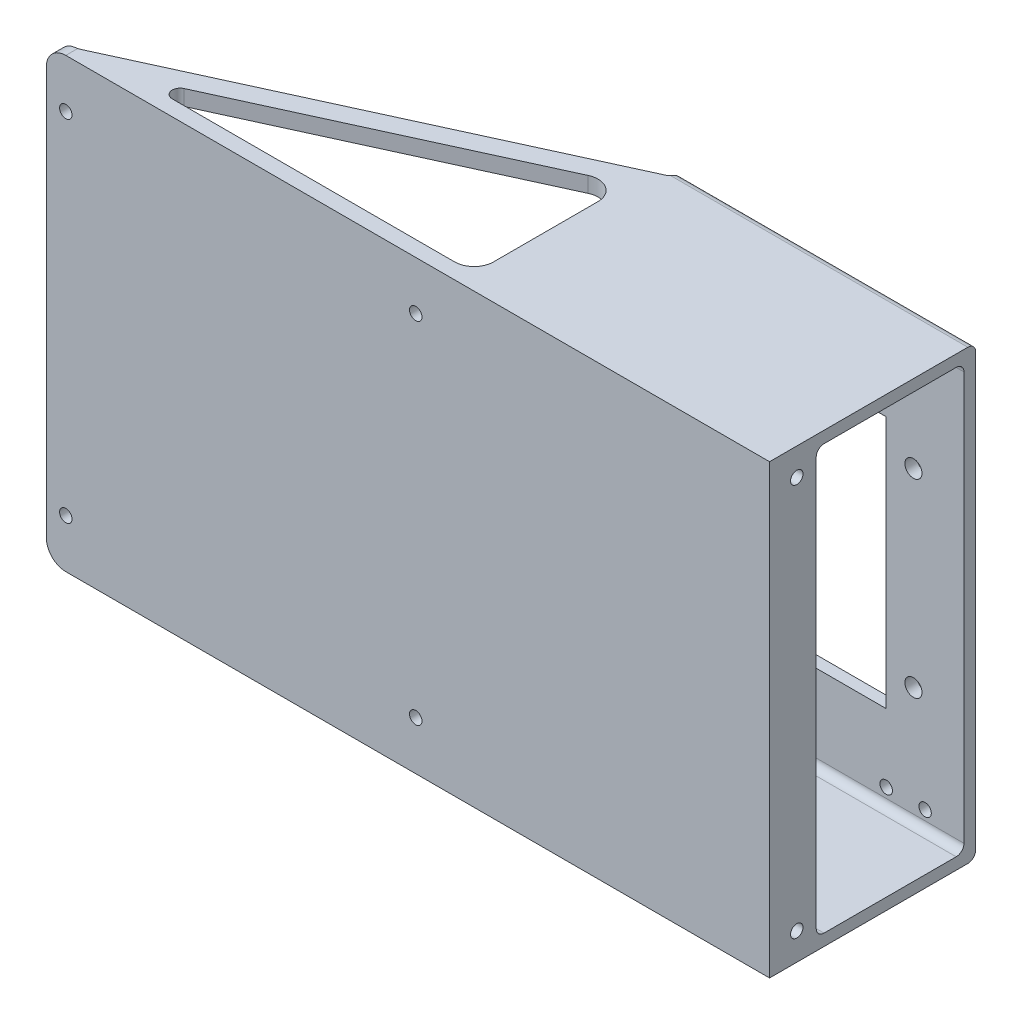
SolidWorks part; units mm, degrees
ref_plane "前视基准面" through (0, 0, 0) normal (0, 0, 1) x (1, 0, 0)
ref_plane "上视基准面" through (0, 0, 0) normal (0, 1, 0) x (1, 0, 0)
ref_plane "右视基准面" through (0, 0, 0) normal (1, 0, 0) x (0, 0, -1)
sketch "草图2" plane through (0, 0, 0) normal (0, 0, 1) x (1, 0, 0)
  line L4 (37.2625, -42.4817) -> (86.0528, -91.2721) construction
  line L5 (23.0528, -9.4817) -> (99.0528, -9.4817)
  line L6 (23.0528, -9.4817) -> (23.0528, -124.4817)
  line L7 (23.0528, -124.4817) -> (99.0528, -124.4817)
  line L8 (99.0528, -9.4817) -> (99.0528, -124.4817)
  line L9 (86.0528, -42.4817) -> (37.2625, -91.2721) construction
  circle A0 centre (86.0528, -91.2721) radius 2.2
  circle A1 centre (86.0528, -42.4817) radius 2.2
  circle A2 centre (37.2625, -42.4817) radius 2.2
  circle A3 centre (37.2625, -91.2721) radius 2.2
  circle A4 centre (89.0528, -16.9817) radius 1.6
  circle A5 centre (79.0528, -16.9817) radius 1.6
  circle A6 centre (41.0528, -16.9817) radius 1.6
  circle A7 centre (51.0528, -16.9817) radius 1.6
  circle A8 centre (41.0528, -116.9817) radius 1.6
  circle A9 centre (51.0528, -116.9817) radius 1.6
  circle A10 centre (79.0528, -116.9817) radius 1.6
  circle A11 centre (89.0528, -116.9817) radius 1.6
  point P12 (64.3101, -80.4099)
  dimension "D4" = 90
  dimension "D5" = 13
  dimension "D6" = 33
  dimension "D7" = 69
  dimension "D8" = 3.2
  dimension "D3" = 69
  dimension "D9" = 10
  dimension "D10" = 7.5
  dimension "D11" = 4.4
  dimension "D12" = 4.4
  dimension "D13" = 4.4
  dimension "D14" = 4.4
  dimension "D18" = 100
  dimension "D1" = 115
  dimension "D2" = 76
  dimension "D15" = 2
  dimension "D16" = 2
  dimension "D17" = 2
extrude "凸台-拉伸1" add sketch "草图2" along normal blind 3
sketch "草图3" plane through (23.0528, 0, 0) normal (-1, 0, 0) x (0, 0, 1)
  line L0 (0, -9.4817) -> (0, -124.4817) construction
  line L1 (0, -9.4817) -> (53, -9.4817)
  line L2 (0, -9.4817) -> (0, -12.4817)
  line L3 (0, -12.4817) -> (50, -12.4817)
  line L8 (50, -12.4817) -> (50, -121.4817)
  line L9 (53, -124.4817) -> (0, -124.4817)
  line L11 (50, -121.4817) -> (0, -121.4817)
  line L12 (0, -124.4817) -> (0, -121.4817)
  line L13 (53, -124.4817) -> (53, -9.4817)
  dimension "D1" = 115
  dimension "D2" = 3
  dimension "D4" = 50
extrude "凸台-拉伸2" add sketch "草图3" against normal blind 76
sketch "草图4" plane through (23.0528, 0, 0) normal (-1, 0, 0) x (0, 0, 1)
  line L0 (3, -12.4817) -> (50, -12.4817) construction
  line L1 (3, -12.4817) -> (50, -12.4817)
  line L2 (3, -12.4817) -> (3, -121.4817)
  line L3 (3, -121.4817) -> (50, -121.4817)
  line L4 (50, -12.4817) -> (50, -121.4817)
  line L5 (3, -12.4817) -> (3, -121.4817) construction
extrude "凸台-拉伸3" add sketch "草图4" against normal blind 3
sketch "草图5" plane through (99.0528, 0, 0) normal (1, 0, 0) x (0, 0, -1)
  line L0 (-53, -124.4817) -> (0, -124.4817) construction
  line L1 (-53, -9.4817) -> (-41, -9.4817)
  line L2 (-53, -9.4817) -> (-53, -124.4817)
  line L3 (-53, -124.4817) -> (-41, -124.4817)
  line L4 (-41, -9.4817) -> (-41, -124.4817)
  circle A0 centre (-46, -117.4817) radius 1.6
  circle A1 centre (-46, -16.4817) radius 1.6
  dimension "D2" = 5
  dimension "D3" = 7
  dimension "D4" = 5
  dimension "D5" = 7
  dimension "D1" = 12
extrude "凸台-拉伸4" add sketch "草图5" against normal blind 3
fillet "圆角1" radius 2 8 edges at (97.5528, -121.4817, 41) (97.5528, -12.4817, 41) (61.0528, -12.4817, 50) (61.0528, -121.4817, 50) (62.5528, -121.4817, 3) (61.0528, -124.4817, 0) (61.0528, -9.4817, 0) (62.5528, -12.4817, 3)
sketch "草图6" plane through (23.0528, 0, 0) normal (-1, 0, 0) x (0, 0, 1)
  line L1 (53, -9.4817) -> (50, -9.4817)
  line L2 (53, -9.4817) -> (53, -124.4817)
  line L3 (53, -124.4817) -> (50, -124.4817)
  line L4 (50, -9.4817) -> (50, -124.4817)
  point P7 (0, 0)
  point P8 (0, 0)
  dimension "D1" = 3
  dimension "D2" = 115
extrude "凸台-拉伸5" add sketch "草图6" along normal blind 110
sketch "草图7" plane through (0, 0, 50) normal (0, 0, -1) x (-1, 0, 0)
  line L0 (86.9472, -9.4817) -> (86.9472, -124.4817) construction
  line L1 (86.9472, -9.4817) -> (-23.0528, -9.4817) construction
  circle A0 centre (81.9472, -21.9817) radius 1.6
  circle A1 centre (81.9472, -111.9817) radius 1.6
  circle A2 centre (-8.0528, -21.9817) radius 1.6
  circle A3 centre (-8.0528, -111.9817) radius 1.6
  dimension "D1" = 5
  dimension "D2" = 12.5
  dimension "D5" = 90
  dimension "D6" = 90
  dimension "D3" = 2
  dimension "D4" = 2
extrude "切除-拉伸1" cut sketch "草图7" against normal blind 110
fillet "圆角2" radius 5 2 edges at (-86.9472, -9.4817, 51.5) (-86.9472, -124.4817, 51.5)
sketch "草图8" plane through (0, 0, 0) normal (0, 0, -1) x (-1, 0, 0)
  line L0 (-99.0528, -122.4817) -> (-99.0528, -11.4817) construction
  line L1 (-79.0528, -34.4817) -> (-48.0528, -34.4817)
  line L2 (-79.0528, -34.4817) -> (-79.0528, -99.4817)
  line L3 (-79.0528, -99.4817) -> (-48.0528, -99.4817)
  line L4 (-48.0528, -34.4817) -> (-48.0528, -99.4817)
  line L5 (-23.0528, -11.4817) -> (-23.0528, -122.4817) construction
  line L6 (-23.0528, -11.4817) -> (-99.0528, -11.4817) construction
  line L7 (-99.0528, -122.4817) -> (-23.0528, -122.4817) construction
  dimension "D1" = 20
  dimension "D2" = 25
  dimension "D3" = 23
  dimension "D4" = 23
extrude "切除-拉伸2" cut sketch "草图8" against normal blind 3
sketch "草图9" plane through (0, -124.4817, 0) normal (0, -1, 0) x (-1, 0, 0)
  line L0 (-23.0528, -2) -> (81.9472, -50)
  line L1 (81.9472, -50) -> (-23.0528, -50)
  line L2 (-23.0528, -50) -> (-23.0528, -2)
extrude "凸台-拉伸6" add sketch "草图9" against normal blind 4
sketch "草图10" plane through (0, -9.4817, 0) normal (0, 1, 0) x (1, 0, 0)
  line L0 (23.0528, -2) -> (-81.9472, -50)
  line L1 (-81.9472, -50) -> (23.0528, -50)
  line L2 (23.0528, -50) -> (23.0528, -2)
extrude "凸台-拉伸7" add sketch "草图10" against normal blind 4
fillet "圆角3" radius 2 9 edges at (-81.9472, -11.4817, 50) (-81.9472, -122.4817, 50) (23.0528, -122.4817, 2) (23.0528, -11.4817, 2) (-29.4472, -13.4817, 50) (23.0528, -13.4817, 26) (23.0528, -66.9817, 50) (-29.4472, -120.4817, 50) (23.0528, -120.4817, 26)
sketch "草图11" plane through (0, -124.4817, 0) normal (0, -1, 0) x (-1, 0, 0)
  line L0 (58.548, -49) -> (-14.0528, -49)
  line L1 (-19.0528, -44) -> (-19.0528, -17.1096)
  line L2 (-11.974, -12.5623) -> (59.3795, -45.1811)
  line L3 (-99.0528, -53) -> (81.9472, -53) construction
  line L4 (-99.0528, -53) -> (-99.0528, -2) construction
  line L5 (81.5511, -49.8189) -> (-21.8844, -2.5342) construction
  arc A0 (-14.0528, -49) -> (-19.0528, -44) centre (-14.0528, -44) cw
  arc A1 (-19.0528, -17.1096) -> (-11.974, -12.5623) centre (-14.0528, -17.1096) cw
  arc A2 (58.548, -49) -> (59.3795, -45.1811) centre (58.548, -47) ccw
  dimension "D4" = 5
  dimension "D5" = 2
  dimension "D1" = 4
  dimension "D2" = 80
  dimension "D3" = 5
extrude "切除-拉伸3" cut sketch "草图11" against normal blind 124
